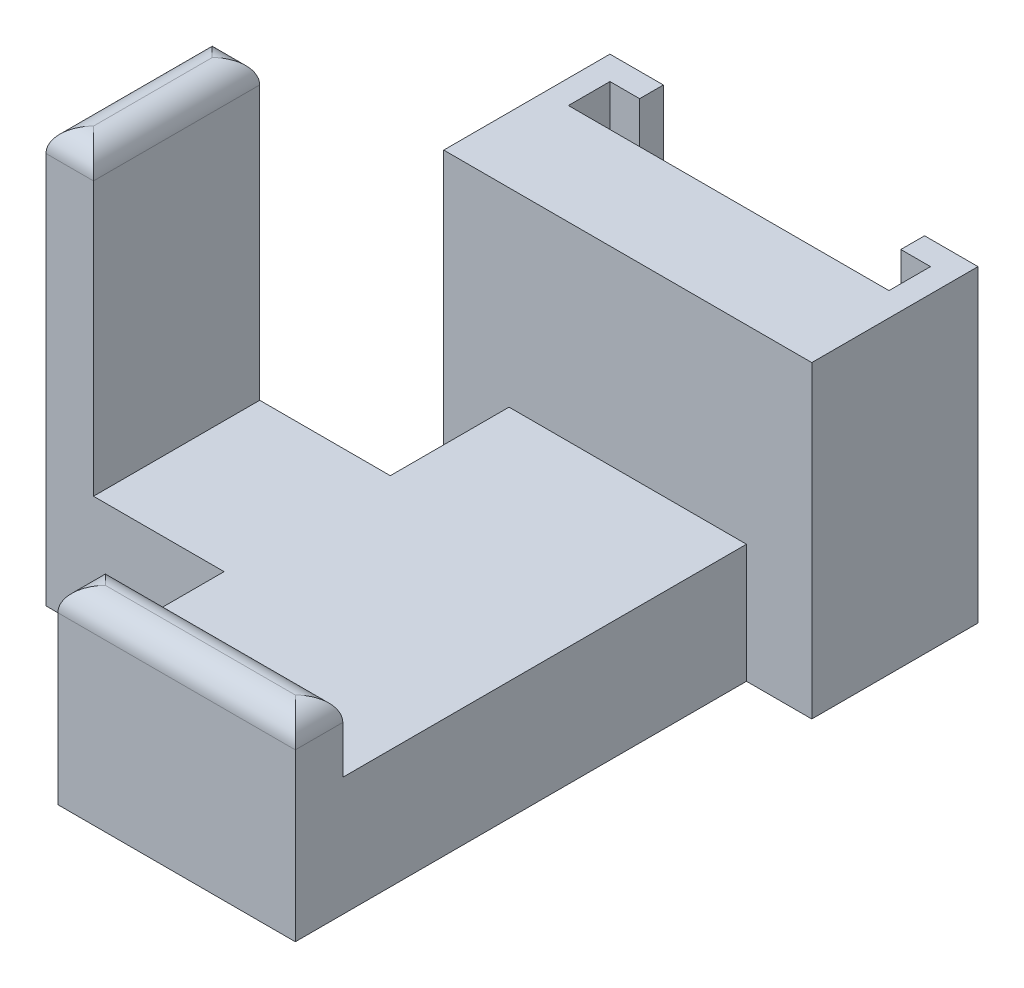
SolidWorks part; units mm, degrees
material "ABS"
ref_plane "Plano frontal" through (0, 0, 0) normal (0, 0, 1) x (1, 0, 0)
ref_plane "Plano superior" through (0, 0, 0) normal (0, 1, 0) x (1, 0, 0)
ref_plane "Plano direito" through (0, 0, 0) normal (1, 0, 0) x (0, 0, -1)
sketch "Esboço1" plane through (0, 0, 0) normal (0, 1, 0) x (1, 0, 0)
  line L0 (0, 28) -> (-15, 28)
  line L1 (0, 0) -> (20, 0)
  line L2 (0, 0) -> (0, 14)
  line L3 (0, 42) -> (20, 42)
  line L4 (20, 0) -> (20, 42)
  line L5 (0, 14) -> (-15, 14)
  line L6 (-15, 14) -> (-15, 28)
  line L7 (0, 28) -> (0, 42)
  line L8 (0, 28) -> (0, 14) construction
  point P5 (0, 21)
  point P12 (-15, 21)
  point P13 (0, 21)
  point P15 (20, 21)
  dimension "D1" = 20
  dimension "D2" = 42
  dimension "D3" = 14
  dimension "D4" = 15
extrude "Ressalto-extrusão1" add sketch "Esboço1" along normal blind 10
sketch "Esboço2" plane through (0, 10, 0) normal (0, 1, 0) x (1, 0, 0)
  line L5 (-15, 14) -> (0, 14) construction
  line L6 (-15, 28) -> (-11, 28)
  line L7 (-15, 28) -> (-15, 14)
  line L8 (-15, 14) -> (-11, 14)
  line L9 (-11, 28) -> (-11, 14)
  line L10 (20, 0) -> (20, 42) construction
  line L11 (0, 0) -> (20, 0)
  line L12 (0, 0) -> (0, 4)
  line L13 (0, 4) -> (20, 4)
  line L14 (20, 0) -> (20, 4)
  line L15 (20, 38) -> (20, 4) construction
  line L16 (0, 14) -> (0, 0) construction
  point P21 (20, 21)
  point P22 (-15, 21)
  dimension "D1" = 4
  dimension "D3" = 4
  dimension "D4" = 34
extrude "Ressalto-extrusão2" add sketch "Esboço2" along normal blind 25
fillet "Filete2" [suppressed] radius 1
fillet "Filete3" [suppressed] radius 1
sketch "Esboço5" plane through (0, 35, 0) normal (0, 1, 0) x (1, 0, 0)
  line L1 (0, 0) -> (20, 0)
  line L2 (0, 0) -> (0, 42)
  line L3 (0, 42) -> (20, 42)
  line L4 (20, 0) -> (20, 42)
extrude "Corte-extrusão1" cut sketch "Esboço5" against normal offset from surface (19 mm away) 6 up to face at (2.25, 10, -22)
fillet "Filete4" radius 2 8 edges at (-13, 35, -28) (-11, 35, -21) (-13, 35, -14) (-15, 35, -21) (20, 16, -2) (10, 16, 0) (0, 16, -2) (10, 16, -4)
sketch "Esboço6" plane through (0, 0, 0) normal (0, -1, 0) x (1, 0, 0)
  line L0 (-15, -21) -> (20, -21) construction
  line L1 (-15, -28) -> (-15, -14) construction
  line L2 (20, 0) -> (20, -42) construction
  line L3 (7.5, -36) -> (7.5, -6)
  point P6 (-13.5, -21)
  point P7 (-7.5, -21)
  point P11 (7.5, -21)
  dimension "D1" = 1.5
  dimension "D2" = 6
  dimension "D3" = 15
  dimension "D4" = 30
sketch "Esboço8" plane through (0, 0, -42) normal (0, 0, -1) x (-1, 0, 0)
  line L0 (-25.5, 0) -> (5.5, 0)
  line L2 (0, 0) -> (15, 0) construction
  line L3 (-25.5, 0) -> (-25.5, 4)
  line L4 (-25.5, 4) -> (5.5, 4)
  line L5 (5.5, 4) -> (5.5, 0)
  line L6 (-20, 0) -> (0, 0) construction
  point P3 (-10, 0)
  point P10 (-10, 0)
  dimension "D1" = 31
  dimension "D2" = 4
extrude "Ressalto-extrusão3" add sketch "Esboço8" along normal blind 10 and the other way blind 4
hole_wizard "Furo de diâmetro Ø4.0 (4)1" positions "3DSketch1" profile "Esboço7" hole size "Ø4.0" standard "ISO"
sketch3d "3DSketch1"
  point P0 (-7.5, 0, -21)
  point P3 (7.5, 0, -6)
sketch "Esboço7" plane through (-7.5, 0, -21) normal (1, 0, 0) x (0, 0, -1)
  line L0 (0, 0) -> (0, 5.2017)
  line L1 (0, 5.2017) -> (2, 4)
  line L2 (2, 4) -> (2, 0)
  line L5 (2, 0) -> (0, 0)
  line L10 (0, 5.2017) -> (-2, 4) construction
  line L11 (0, -6.35) -> (0, 107.95) construction
  dimension "Hole Dia." = 4
  dimension "Hole Depth" = 4
  dimension "Drill Angle" = 118
sketch "Esboço9" plane through (0, 4, 0) normal (0, 1, 0) x (1, 0, 0)
  line L1 (0, 38) -> (0, 42) construction
  line L2 (-3.5, 46.5) -> (-3.5, 50)
  line L3 (-3.5, 50) -> (23.5, 50)
  line L4 (23.5, 50) -> (23.5, 46.5)
  line L7 (20, 42) -> (20, 38)
  line L8 (20, 38) -> (25.5, 38)
  line L9 (25.5, 38) -> (25.5, 52)
  line L10 (25.5, 52) -> (-5.5, 52)
  line L11 (-5.5, 52) -> (-5.5, 38)
  line L12 (-5.5, 38) -> (0, 38)
  line L13 (0, 38) -> (0, 42)
  line L15 (-3.5, 46.5) -> (23.5, 46.5)
  line L16 (0, 42) -> (20, 42)
  dimension "D1" = 2
  dimension "D2" = 2
  dimension "D3" = 2
  dimension "D4" = 3.5
extrude "Ressalto-extrusão4" add sketch "Esboço9" along normal blind 22
sketch "Esboço10" plane through (0, 10, 0) normal (0, 1, 0) x (1, 0, 0)
  line L0 (0, 38) -> (0, 42)
  line L1 (0, 42) -> (0, 38) construction
  line L3 (0, 42) -> (20, 42)
  line L4 (20, 42) -> (20, 38)
  line L5 (20, 38) -> (0, 38)
  line L6 (20, 42) -> (0, 42) construction
extrude "Ressalto-extrusão5" add sketch "Esboço10" along normal up to surface (16 mm away) up to face at (10, 26, -42.5)
sketch "Esboço11" plane through (0, 0, -52) normal (0, 0, -1) x (-1, 0, 0)
  line L0 (-21, 26) -> (1, 26)
  line L1 (-25.5, 26) -> (5.5, 26) construction
  line L2 (-21, 26) -> (-21, 14)
  line L3 (-21, 14) -> (1, 14)
  line L4 (1, 14) -> (1, 26)
  line L5 (-25.5, 0) -> (5.5, 0) construction
  point P5 (-10, 26)
  point P11 (-10, 0)
  dimension "D1" = 22
  dimension "D2" = 12
extrude "Corte-extrusão2" cut sketch "Esboço11" against normal up to surface (2 mm away) up to face at (10, 15, -50)
